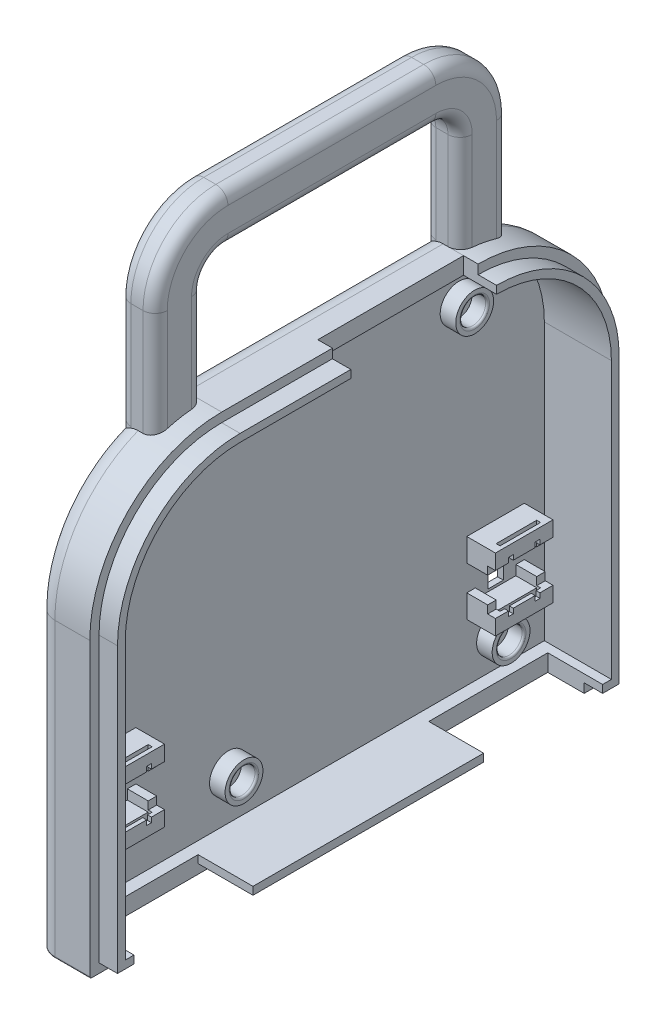
SolidWorks part; units mm, degrees
ref_plane "Front Plane" through (0, 0, 0) normal (0, 0, 1) x (1, 0, 0)
ref_plane "Top Plane" through (0, 0, 0) normal (0, 1, 0) x (1, 0, 0)
ref_plane "Right Plane" through (0, 0, 0) normal (1, 0, 0) x (0, 0, -1)
sketch "Sketch1" plane through (0, 0, 0) normal (1, 0, 0) x (0, 0, -1)
  line L0 (-52.8, 99.65) -> (52.8, 99.65)
  line L1 (-107.1, 45.35) -> (-107.1, -45.35)
  line L2 (-70, -75.35) -> (70, -75.35)
  line L3 (107.1, 45.35) -> (107.1, -45.35)
  line L4 (107.1, 0) -> (-107.1, 0) construction
  line L5 (0, 99.65) -> (0, -75.35) construction
  line L11 (107.1, -45.35) -> (107.1, -75.35)
  line L12 (107.1, -75.35) -> (70, -75.35)
  line L13 (-83.2, -21.7) -> (-76.8, -21.7)
  line L14 (-83.2, -21.7) -> (-83.2, -38.3)
  line L15 (-83.2, -38.3) -> (-76.8, -38.3)
  line L16 (-76.8, -21.7) -> (-76.8, -38.3)
  line L17 (-83.2, -21.7) -> (-76.8, -38.3) construction
  line L18 (-83.2, -38.3) -> (-76.8, -21.7) construction
  line L19 (76.8, -21.7) -> (83.2, -21.7)
  line L20 (76.8, -21.7) -> (76.8, -38.3)
  line L21 (76.8, -38.3) -> (83.2, -38.3)
  line L22 (83.2, -21.7) -> (83.2, -38.3)
  line L23 (76.8, -21.7) -> (83.2, -38.3) construction
  line L24 (76.8, -38.3) -> (83.2, -21.7) construction
  line L25 (80, -30) -> (-80, -30) construction
  line L27 (-107.1, -45.35) -> (-107.1, -75.35)
  line L28 (-107.1, -75.35) -> (-70, -75.35)
  arc A0 (52.8, 99.65) -> (107.1, 45.35) centre (52.8, 45.35) cw
  arc A1 (-52.8, 99.65) -> (-107.1, 45.35) centre (-52.8, 45.35) ccw
  point P16 (0, 0)
  point P17 (-80, -30)
  point P32 (80, -30)
  point P39 (-80, -30)
  point P40 (0, -30)
  dimension "D4" = 54.3
  dimension "D2" = 175
  dimension "D3" = 214.2
  dimension "D5" = 140
  dimension "D6" = 30
  dimension "D7" = 160
  dimension "D8" = 6.4
  dimension "D9" = 16.6
  dimension "D10" = 6.4
  dimension "D11" = 16.6
  dimension "D12" = 30
extrude "Boss-Extrude1" add sketch "Sketch1" along normal blind 2.4
sketch "Sketch9" plane through (2.4, 0, 0) normal (1, 0, 0) x (0, 0, -1)
  line L17 (52.8, 99.65) -> (-52.8, 99.65)
  line L31 (52.8, 99.65) -> (-52.8, 99.65)
  line L32 (-107.1, 45.35) -> (-107.1, -75.35)
  line L33 (-107.1, 45.35) -> (-107.1, -75.35)
  line L34 (-107.1, -75.35) -> (107.1, -75.35)
  line L39 (107.1, -75.35) -> (107.1, 45.35)
  line L43 (107.1, -75.35) -> (107.1, 45.35)
  line L45 (-107.1, -75.35) -> (107.1, -75.35)
  arc A15 (-52.8, 99.65) -> (-107.1, 45.35) centre (-52.8, 45.35) ccw
  arc A16 (-52.8, 99.65) -> (-107.1, 45.35) centre (-52.8, 45.35) ccw
  arc A17 (107.1, 45.35) -> (52.8, 99.65) centre (52.8, 45.35) ccw
  arc A18 (107.1, 45.35) -> (52.8, 99.65) centre (52.8, 45.35) ccw
  dimension "D1" = 0
sketch "Sketch10" plane through (2.4, 0, 0) normal (1, 0, 0) x (0, 0, -1)
  line L0 (65, -55.35) -> (0, -55.35) construction
  line L1 (-65, -55.35) -> (65, -55.35) construction
  line L2 (-65, -55.35) -> (-65, 54.65) construction
  line L3 (-65, 54.65) -> (65, 54.65) construction
  line L4 (65, -55.35) -> (65, 54.65) construction
  line L5 (-65, -55.35) -> (65, 54.65) construction
  line L6 (-65, 54.65) -> (65, -55.35) construction
  line L7 (0, -55.35) -> (-65, -55.35) construction
  line L8 (-107.1, -75.35) -> (107.1, -75.35) construction
  line L9 (0, -0.35) -> (0, 0) construction
  line L10 (0, -0.35) -> (0, -50.35) construction
  line L11 (-65, 54.65) -> (-65, 70.65) construction
  line L12 (-65, 70.65) -> (-70, 70.65) construction
  line L13 (0, -50.35) -> (-30, -50.35) construction
  circle A11 centre (-30, -50.35) radius 2.3
  circle A13 centre (65, 69.65) radius 2.3
  circle A14 centre (80, -55.35) radius 2.3
  circle A15 centre (-70, 70.65) radius 2.3
  point P0 (0, -0.35)
  point P11 (0, -55.35)
  point P12 (32.5, -55.35)
  point P14 (-32.5, -55.35)
  dimension "D3" = 15
  dimension "D4" = 20
  dimension "D8" = 4.6
  dimension "D1" = 130
  dimension "D2" = 110
  dimension "D5" = 50
  dimension "D6" = 15
  dimension "D7" = 16
  dimension "D9" = 5
  dimension "D10" = 30
extrude "Cut-Extrude1" cut sketch "Sketch10" against normal blind 100 and the other way blind 1000
sketch "Sketch12" plane through (2.4, 0, 0) normal (1, 0, 0) x (0, 0, -1)
  line L5 (-88.35, -38.3) -> (-88.35, -35.3)
  line L6 (-88.35, -38.3) -> (-88.35, -21.7) construction
  line L22 (71.65, -38.3) -> (71.65, -35.3)
  line L23 (71.65, -38.3) -> (71.65, -21.7) construction
  line L24 (71.65, -38.3) -> (88.35, -38.3) construction
  line L25 (88.35, -38.3) -> (88.35, -21.7) construction
  line L26 (71.65, -21.7) -> (88.35, -21.7) construction
  line L27 (71.65, -38.3) -> (88.35, -21.7) construction
  line L28 (88.35, -38.3) -> (71.65, -21.7) construction
  line L29 (71.65, -21.7) -> (71.65, -24.7)
  line L30 (88.35, -38.3) -> (88.35, -35.3)
  line L31 (88.35, -21.7) -> (88.35, -24.7)
  line L32 (71.65, -21.7) -> (88.35, -21.7) construction
  line L33 (88.35, -38.3) -> (71.65, -38.3) construction
  line L34 (88.35, -35.3) -> (91.85, -35.3)
  line L35 (71.65, -35.3) -> (68.15, -35.3)
  line L36 (68.15, -35.3) -> (68.15, -41.8)
  line L37 (68.15, -41.8) -> (91.85, -41.8)
  line L38 (91.85, -41.8) -> (91.85, -35.3)
  line L39 (71.65, -24.7) -> (68.15, -24.7)
  line L40 (68.15, -24.7) -> (68.15, -18.2)
  line L41 (68.15, -18.2) -> (91.85, -18.2)
  line L42 (91.85, -18.2) -> (91.85, -24.7)
  line L43 (91.85, -24.7) -> (88.35, -24.7)
  line L44 (83.2, -38.3) -> (76.8, -21.7) construction
  line L45 (83.2, -21.7) -> (76.8, -38.3) construction
  line L46 (-88.35, -38.3) -> (-71.65, -38.3) construction
  line L47 (-71.65, -38.3) -> (-71.65, -21.7) construction
  line L48 (-88.35, -21.7) -> (-71.65, -21.7) construction
  line L49 (-88.35, -38.3) -> (-71.65, -21.7) construction
  line L50 (-71.65, -38.3) -> (-88.35, -21.7) construction
  line L51 (-88.35, -21.7) -> (-88.35, -24.7)
  line L52 (-71.65, -38.3) -> (-71.65, -35.3)
  line L53 (-71.65, -21.7) -> (-71.65, -24.7)
  line L54 (-88.35, -21.7) -> (-71.65, -21.7) construction
  line L55 (-71.65, -38.3) -> (-88.35, -38.3) construction
  line L56 (-71.65, -35.3) -> (-68.15, -35.3)
  line L57 (-88.35, -35.3) -> (-91.85, -35.3)
  line L58 (-91.85, -35.3) -> (-91.85, -41.8)
  line L59 (-91.85, -41.8) -> (-68.15, -41.8)
  line L60 (-68.15, -41.8) -> (-68.15, -35.3)
  line L61 (-88.35, -24.7) -> (-91.85, -24.7)
  line L62 (-91.85, -24.7) -> (-91.85, -18.2)
  line L63 (-91.85, -18.2) -> (-68.15, -18.2)
  line L64 (-68.15, -18.2) -> (-68.15, -24.7)
  line L65 (-68.15, -24.7) -> (-71.65, -24.7)
  line L66 (-76.8, -38.3) -> (-83.2, -21.7) construction
  line L67 (-83.2, -38.3) -> (-76.8, -21.7) construction
  line L68 (-88.35, -21.7) -> (-88.35, -20.7047)
  line L69 (-88.35, -20.7047) -> (-71.65, -20.7047)
  line L70 (-71.65, -20.7047) -> (-71.65, -21.7)
  line L71 (-88.35, -38.3) -> (-88.35, -39.3)
  line L72 (-88.35, -39.3) -> (-71.65, -39.3)
  line L73 (-71.65, -39.3) -> (-71.65, -38.3)
  line L74 (88.35, -38.3) -> (88.35, -39.3)
  line L75 (88.35, -39.3) -> (71.65, -39.3)
  line L76 (71.65, -39.3) -> (71.65, -38.3)
  line L77 (88.35, -21.7) -> (88.35, -20.7047)
  line L78 (88.35, -20.7047) -> (71.65, -20.7047)
  line L79 (71.65, -20.7047) -> (71.65, -21.7)
  point P3 (-0.1438, 64.1533)
  point P4 (-80, -30)
  point P19 (80, -30)
  point P21 (-80, -30)
  point P30 (380.6447, 32.9453)
  point P31 (130.7088, -20.4974)
  point P32 (80, -30)
  point P49 (169.9078, -49.5925)
  dimension "D3" = 16.7
  dimension "D4" = 16.6
  dimension "D5" = 10.6
  dimension "D6" = 3.5
  dimension "D7" = 3.5
  dimension "D8" = 3.5
  dimension "D9" = 3.5
  dimension "D10" = 4.9497
  dimension "D11" = 16.7
  dimension "D12" = 16.6
  dimension "D13" = 10.6
  dimension "D14" = 3.5
  dimension "D15" = 3.5
  dimension "D16" = 3.5
  dimension "D17" = 3.5
  dimension "D18" = 4.9497
  dimension "D19" = 4.9497
  dimension "D20" = 7.3824
  dimension "D21" = 23.5468
  dimension "D22" = 24.088
  dimension "D23" = 4.9497
  dimension "D24" = 7.3824
  dimension "D25" = 23.5468
  dimension "D26" = 24.088
  dimension "D27" = 0.9953
  dimension "D28" = 1
  dimension "D29" = 1
  dimension "D30" = 0.9953
extrude "Boss-Extrude2" add sketch "Sketch12" along normal blind 8.6
sketch "Sketch14" plane through (11, 0, 0) normal (1, 0, 0) x (0, 0, -1)
  line L0 (-91.85, -18.2) -> (-91.85, -24.7) construction
  line L1 (-91.85, -18.2) -> (-68.15, -18.2)
  line L2 (-91.85, -18.2) -> (-91.85, -21.45)
  line L3 (-91.85, -21.45) -> (-68.15, -21.45)
  line L4 (-68.15, -18.2) -> (-68.15, -21.45)
  line L5 (-68.15, -18.2) -> (-91.85, -18.2) construction
  line L6 (-68.15, -24.7) -> (-68.15, -18.2) construction
  line L7 (-68.15, -41.8) -> (-68.15, -35.3) construction
  line L8 (-91.85, -41.8) -> (-68.15, -41.8)
  line L9 (-91.85, -41.8) -> (-91.85, -38.55)
  line L10 (-91.85, -38.55) -> (-68.15, -38.55)
  line L11 (-68.15, -41.8) -> (-68.15, -38.55)
  line L12 (91.85, -41.8) -> (91.85, -35.3) construction
  line L13 (68.15, -41.8) -> (91.85, -41.8)
  line L14 (68.15, -41.8) -> (68.15, -38.55)
  line L15 (68.15, -38.55) -> (91.85, -38.55)
  line L16 (91.85, -41.8) -> (91.85, -38.55)
  line L17 (91.85, -24.7) -> (91.85, -18.2) construction
  line L18 (68.15, -18.2) -> (91.85, -18.2)
  line L19 (68.15, -18.2) -> (68.15, -21.45)
  line L20 (68.15, -21.45) -> (91.85, -21.45)
  line L21 (91.85, -18.2) -> (91.85, -21.45)
extrude "Boss-Extrude3" add sketch "Sketch14" along normal blind 3.2
sketch "Sketch17" plane through (0, 0, 0) normal (1, 0, 0) x (0, 0, -1)
  line L0 (-103.9, 45.35) -> (-103.9, -72.15) construction
  line L1 (-103.9, -72.15) -> (103.9, -72.15) construction
  line L2 (103.9, -72.15) -> (103.9, 45.35) construction
  line L3 (52.8, 96.45) -> (-52.8, 96.45) construction
  line L4 (52.8, 99.65) -> (-52.8, 99.65)
  line L5 (-107.1, 45.35) -> (-107.1, -75.35)
  line L6 (-107.1, -75.35) -> (107.1, -75.35)
  line L7 (107.1, -75.35) -> (107.1, 45.35)
  line L8 (52.8, 99.65) -> (-52.8, 99.65) construction
  line L9 (-107.1, 45.35) -> (-107.1, -75.35) construction
  line L11 (107.1, -75.35) -> (107.1, 45.35) construction
  line L16 (100.1, -68.35) -> (100.1, 45.35)
  line L17 (52.8, 92.65) -> (-52.8, 92.65)
  line L18 (-100.1, 45.35) -> (-100.1, -68.35)
  line L19 (-100.1, -68.35) -> (100.1, -68.35)
  line L24 (52.8, 95.85) -> (-52.8, 95.85)
  line L25 (-103.3, 45.35) -> (-103.3, -71.55)
  line L27 (103.3, -71.55) -> (103.3, 45.35)
  line L28 (-107.1, -75.35) -> (107.1, -75.35) construction
  line L29 (-103.3, -71.55) -> (103.3, -71.55) construction
  line L31 (-103.3, -71.55) -> (103.3, -71.55)
  arc A0 (103.9, 45.35) -> (52.8, 96.45) centre (52.8, 45.35) ccw construction
  arc A1 (-52.8, 96.45) -> (-103.9, 45.35) centre (-52.8, 45.35) ccw construction
  arc A2 (-52.8, 99.65) -> (-107.1, 45.35) centre (-52.8, 45.35) ccw
  arc A3 (107.1, 45.35) -> (52.8, 99.65) centre (52.8, 45.35) ccw
  arc A4 (-52.8, 99.65) -> (-107.1, 45.35) centre (-52.8, 45.35) ccw construction
  arc A5 (107.1, 45.35) -> (52.8, 99.65) centre (52.8, 45.35) ccw construction
  arc A8 (100.1, 45.35) -> (52.8, 92.65) centre (52.8, 45.35) ccw
  arc A9 (-52.8, 92.65) -> (-100.1, 45.35) centre (-52.8, 45.35) ccw
  arc A12 (-52.8, 95.85) -> (-103.3, 45.35) centre (-52.8, 45.35) ccw
  arc A13 (103.3, 45.35) -> (52.8, 95.85) centre (52.8, 45.35) ccw
  dimension "D4" = 167.4
  dimension "D5" = 206.6
  dimension "D7" = 207.8
  dimension "D8" = 214.2
  dimension "D9" = 3.2
  dimension "D2" = 3.2
  dimension "D10" = 3.2
  dimension "D11" = 3.2
  dimension "D1" = 0
  dimension "D3" = 3.2
  dimension "D6" = 0.6
extrude "Boss-Extrude4" add sketch "Sketch17" along normal blind 30
sketch "Sketch21" plane through (2.4, 0, 0) normal (1, 0, 0) x (0, 0, -1)
  line L4 (-107.1, -75.35) -> (107.1, -75.35)
  line L6 (-107.1, -75.35) -> (107.1, -75.35)
  line L8 (52.8, 99.65) -> (-52.8, 99.65)
  line L9 (-107.1, 45.35) -> (-107.1, -75.35)
  line L11 (107.1, -75.35) -> (107.1, 45.35)
  line L12 (52.8, 99.65) -> (-52.8, 99.65)
  line L13 (-107.1, 45.35) -> (-107.1, -75.35)
  line L15 (107.1, -75.35) -> (107.1, 45.35)
  arc A4 (-52.8, 99.65) -> (-107.1, 45.35) centre (-52.8, 45.35) ccw
  arc A5 (107.1, 45.35) -> (52.8, 99.65) centre (52.8, 45.35) ccw
  arc A6 (-52.8, 99.65) -> (-107.1, 45.35) centre (-52.8, 45.35) ccw
  arc A7 (107.1, 45.35) -> (52.8, 99.65) centre (52.8, 45.35) ccw
  dimension "D1" = 0
sketch "Sketch22" plane through (2.4, 0, 0) normal (1, 0, 0) x (0, 0, -1)
  line L0 (-107.1, -75.35) -> (107.1, -75.35) construction
  line L1 (-107.1, -75.35) -> (107.1, -75.35)
  line L21 (52.8, 99.65) -> (-52.8, 99.65)
  line L22 (107.1, -75.35) -> (107.1, 45.35)
  line L24 (-107.1, 45.35) -> (-107.1, -75.35)
  line L25 (52.8, 99.65) -> (-52.8, 99.65)
  line L26 (107.1, -75.35) -> (107.1, 45.35)
  line L28 (-107.1, 45.35) -> (-107.1, -75.35)
  line L44 (-103.3, -71.55) -> (103.3, -71.55)
  line L45 (103.3, -71.55) -> (103.3, 45.35)
  line L46 (52.8, 95.85) -> (-52.8, 95.85)
  line L47 (-103.3, 45.35) -> (-103.3, -71.55)
  line L48 (-103.3, -71.55) -> (103.3, -71.55)
  line L49 (103.3, -71.55) -> (103.3, 45.35)
  line L50 (52.8, 95.85) -> (-52.8, 95.85)
  line L51 (-103.3, 45.35) -> (-103.3, -71.55)
  arc A6 (-52.8, 99.65) -> (-107.1, 45.35) centre (-52.8, 45.35) ccw
  arc A7 (107.1, 45.35) -> (52.8, 99.65) centre (52.8, 45.35) ccw
  arc A8 (-52.8, 99.65) -> (-107.1, 45.35) centre (-52.8, 45.35) ccw
  arc A9 (107.1, 45.35) -> (52.8, 99.65) centre (52.8, 45.35) ccw
  arc A20 (103.3, 45.35) -> (52.8, 95.85) centre (52.8, 45.35) ccw
  arc A21 (-52.8, 95.85) -> (-103.3, 45.35) centre (-52.8, 45.35) ccw
  arc A22 (103.3, 45.35) -> (52.8, 95.85) centre (52.8, 45.35) ccw
  arc A23 (-52.8, 95.85) -> (-103.3, 45.35) centre (-52.8, 45.35) ccw
  dimension "D1" = 0
  dimension "D2" = 0
extrude "Boss-Extrude7" add sketch "Sketch22" along normal blind 20
sketch "Sketch23" plane through (0, -75.35, 0) normal (0, -1, 0) x (1, 0, 0)
  line L0 (0, 99.1) -> (0, 107.1)
  line L1 (0, 107.1) -> (8, 107.1)
  line L2 (8, -107.1) -> (0, -107.1)
  line L3 (0, -107.1) -> (0, -99.1)
  line L8 (0, 107.1) -> (0, -107.1)
  line L9 (0, -107.1) -> (22.4, -107.1)
  line L10 (22.4, -107.1) -> (22.4, 107.1)
  line L11 (22.4, 107.1) -> (0, 107.1)
  line L12 (0, 99.1) -> (0, -99.1) construction
  line L13 (8, -107.1) -> (22.4, -107.1) construction
  line L15 (22.4, 107.1) -> (8, 107.1) construction
  arc A0 (0, 99.1) -> (8, 107.1) centre (8, 99.1) cw
  arc A1 (0, -99.1) -> (8, -107.1) centre (8, -99.1) ccw
  dimension "D2" = 8
  dimension "D1" = 0
extrude "Cut-Extrude4" cut sketch "Sketch23" against normal through all
fillet "Fillet4" radius 8 3 edges at (0, 92.7258, 79.3335) (0, 99.65, 0) (0, 92.7258, -79.3335)
sketch "Sketch26" plane through (22.4, 0, 0) normal (1, 0, 0) x (0, 0, -1)
  line L1 (-47.5, -68.3365) -> (47.5, -68.3365)
  line L2 (47.5, -68.3365) -> (47.5, -71.55)
  line L6 (47.5, -71.55) -> (-47.5, -71.55)
  line L7 (-47.5, -71.55) -> (-47.5, -68.3365)
  line L8 (-103.3, -71.55) -> (103.3, -71.55) construction
  line L9 (-96.5, -79.5369) -> (96.5, -79.5369)
  line L10 (-96.5, -79.5369) -> (-96.5, -63.5631)
  line L11 (-96.5, -63.5631) -> (96.5, -63.5631)
  line L12 (96.5, -79.5369) -> (96.5, -63.5631)
  line L13 (-96.5, -79.5369) -> (96.5, -63.5631) construction
  line L14 (-96.5, -63.5631) -> (96.5, -79.5369) construction
  line L15 (107.1, -75.35) -> (107.1, 45.35) construction
  point P0 (0, -71.55)
  point P9 (0, -68.3365)
  point P13 (0, -68.3365)
  point P16 (0, -68.3365)
  dimension "D1" = 10.6
  dimension "D2" = 15.9739
  dimension "D3" = 95
  dimension "D4" = 3.2135
extrude "Cut-Extrude7" cut sketch "Sketch26" against normal blind 15 and the other way blind 20
sketch "Sketch28" plane through (0, 99.65, 0) normal (0, 1, 0) x (1, 0, 0)
  line L0 (22.4, 52.8) -> (16.4, 52.8)
  line L1 (22.4, 52.8) -> (8, 52.8) construction
  line L2 (16.4, 52.8) -> (16.4, -7.2)
  line L3 (16.4, -7.2) -> (51.1003, -7.2)
  line L4 (51.1003, -7.2) -> (51.1003, 52.8)
  line L5 (51.1003, 52.8) -> (22.4, 52.8)
  dimension "D1" = 6
  dimension "D2" = 60
extrude "Cut-Extrude8" cut sketch "Sketch28" against normal blind 10
sketch "Sketch29" plane through (0, -21.45, 0) normal (0, -1, 0) x (1, 0, 0)
  line L12 (11, -88.35) -> (11, -91.85) construction
  line L13 (11, -82.1) -> (11, -98.1)
  line L14 (11, -98.1) -> (12.5, -98.1)
  line L15 (12.5, -98.1) -> (12.5, -82.1)
  line L16 (12.5, -82.1) -> (11, -82.1)
  line L23 (2.4, 68.15) -> (14.2, 68.15)
  line L24 (2.4, 91.85) -> (2.4, 68.15)
  line L25 (14.2, 91.85) -> (2.4, 91.85)
  line L26 (14.2, 68.15) -> (14.2, 91.85)
  line L31 (2.4, 68.15) -> (14.2, 68.15) construction
  line L32 (2.4, 91.85) -> (2.4, 68.15) construction
  line L33 (14.2, 91.85) -> (2.4, 91.85) construction
  line L34 (14.2, 68.15) -> (14.2, 91.85) construction
  point P1 (11, -90.1)
  point P9 (11, -90.1)
  point P14 (11, -90.1)
  dimension "D1" = 0
  dimension "D3" = 16
  dimension "D4" = 1.5
sketch "Sketch30" plane through (2.4, 0, 0) normal (1, 0, 0) x (0, 0, -1)
  circle A0 centre (-70, 70.65) radius 5.3
  circle A1 centre (65, 69.65) radius 5.3
  circle A2 centre (-30, -50.35) radius 5.3
  circle A3 centre (80, -55.35) radius 5.3
  circle A5 centre (65, 69.65) radius 7.8
  circle A6 centre (80, -55.35) radius 7.8
  circle A7 centre (-30, -50.35) radius 7.8
  circle A8 centre (-70, 70.65) radius 7.8
  dimension "D1" = 10.6
  dimension "D2" = 15.6
extrude "Boss-Extrude8" add sketch "Sketch30" along normal blind 6.4
fillet "Fillet7" radius 0.8 4 edges at (8.8, -55.35, -85.3) (8.8, -50.35, 24.7) (8.8, 69.65, -70.3) (8.8, 70.65, 64.7)
fillet "Fillet8" radius 0.8 5 edges at (15.2, -75.35, 107.1) (2.3431, -75.35, 104.7569) (15.2, -75.35, -107.1) (2.3431, -75.35, -104.7569) (0, -75.35, 0)
sketch "Sketch31" plane through (0, 0, 0) normal (1, 0, 0) x (0, 0, -1)
  line L0 (-52.8, 99.65) -> (-52.8, 139.65)
  line L1 (-42.8, 149.65) -> (42.8, 149.65)
  line L2 (52.8, 139.65) -> (52.8, 99.65)
  line L3 (52.8, 99.65) -> (-52.8, 99.65) construction
  line L4 (-72.8, 95.8326) -> (-72.8, 139.65)
  line L5 (-42.8, 169.65) -> (42.8, 169.65)
  line L6 (72.8, 139.65) -> (72.8, 95.8326)
  arc A2 (-52.8, 99.65) -> (-107.1, 45.35) centre (-52.8, 45.35) ccw construction
  arc A3 (107.1, 45.35) -> (52.8, 99.65) centre (52.8, 45.35) ccw construction
  arc A4 (-52.8, 99.65) -> (-72.8, 95.8326) centre (-52.8, 45.35) ccw
  arc A5 (72.8, 95.8326) -> (52.8, 99.65) centre (52.8, 45.35) ccw
  arc A9 (-52.8, 139.65) -> (-42.8, 149.65) centre (-42.8, 139.65) cw
  arc A10 (42.8, 149.65) -> (52.8, 139.65) centre (42.8, 139.65) cw
  arc A11 (72.8, 139.65) -> (42.8, 169.65) centre (42.8, 139.65) ccw
  arc A12 (-42.8, 169.65) -> (-72.8, 139.65) centre (-42.8, 139.65) ccw
  point P13 (52.8, 149.65)
  dimension "D2" = 10
  dimension "D1" = 50
  dimension "D3" = 20
  dimension "D4" = 20
extrude "Boss-Extrude9" add sketch "Sketch31" along normal blind 15
fillet "Fillet9" radius 5 20 edges at (0, 117.7413, -72.8) (0, 160.8632, -64.0132) (0, 117.7413, 72.8) (0, 160.8632, 64.0132) (0, 119.65, 52.8) (0, 146.7211, 49.8711) (0, 149.65, 0) (0, 146.7211, -49.8711) (15, 119.65, 52.8) (15, 119.65, -52.8) (15, 146.7211, -49.8711) (15, 149.65, 0) (15, 117.7413, -72.8) (15, 160.8632, -64.0132) (15, 169.65, 0) (15, 117.7413, 72.8) (0, 169.65, 0) (0, 119.65, -52.8) (15, 146.7211, 49.8711) (15, 160.8632, 64.0132)
sketch "Sketch32" plane through (0, 0, 0) normal (-1, 0, 0) x (0, 0, 1)
  line L0 (52.8, 99.65) -> (52.8, 91.65)
  line L1 (72.8, 95.8326) -> (72.8, 87.1075)
  line L2 (-72.8, 95.8326) -> (-72.8, 87.1075)
  line L3 (-52.8, 99.65) -> (-52.8, 91.65)
  arc A0 (67.8, 97.5371) -> (57.8, 99.4193) centre (52.8, 45.35) ccw construction
  arc A1 (-52.8, 91.65) -> (-99.1, 45.35) centre (-52.8, 45.35) ccw construction
  arc A2 (-52.8, 99.65) -> (-57.8, 99.4193) centre (-52.8, 45.35) ccw construction
  arc A3 (-57.8, 99.4193) -> (-67.8, 97.5371) centre (-52.8, 45.35) ccw construction
  arc A4 (-67.8, 97.5371) -> (-72.8, 95.8326) centre (-52.8, 45.35) ccw construction
  arc A5 (72.8, 95.8326) -> (67.8, 97.5371) centre (52.8, 45.35) ccw construction
  arc A6 (57.8, 99.4193) -> (52.8, 99.65) centre (52.8, 45.35) ccw construction
  arc A7 (99.1, 45.35) -> (52.8, 91.65) centre (52.8, 45.35) ccw construction
  arc A8 (67.8, 97.5371) -> (57.8, 99.4193) centre (52.8, 45.35) ccw
  arc A9 (-52.8, 91.65) -> (-72.8, 87.1075) centre (-52.8, 45.35) ccw
  arc A10 (-52.8, 99.65) -> (-57.8, 99.4193) centre (-52.8, 45.35) ccw
  arc A11 (-57.8, 99.4193) -> (-67.8, 97.5371) centre (-52.8, 45.35) ccw
  arc A12 (-67.8, 97.5371) -> (-72.8, 95.8326) centre (-52.8, 45.35) ccw
  arc A13 (72.8, 95.8326) -> (67.8, 97.5371) centre (52.8, 45.35) ccw
  arc A14 (57.8, 99.4193) -> (52.8, 99.65) centre (52.8, 45.35) ccw
  arc A15 (72.8, 87.1075) -> (52.8, 91.65) centre (52.8, 45.35) ccw
extrude "Boss-Extrude10" add sketch "Sketch32" against normal up to body separate body
fillet "Fillet10" radius 5 4 edges at (0, 91.47, 72.8) (0, 95.65, 52.8) (0, 95.65, -52.8) (0, 91.47, -72.8)
sketch "Sketch33" plane through (0, -38.55, 0) normal (0, 1, 0) x (1, 0, 0)
  line L0 (11, 91.85) -> (11, 88.35) construction
  line L1 (11, 88.35) -> (11, 71.65) construction
  line L2 (11, 71.65) -> (11, 68.15) construction
  line L3 (11, 68.15) -> (14.2, 68.15) construction
  line L4 (14.2, 68.15) -> (14.2, 91.85) construction
  line L5 (14.2, 91.85) -> (11, 91.85) construction
  line L6 (11, -68.15) -> (11, -71.65) construction
  line L7 (11, -71.65) -> (11, -88.35) construction
  line L8 (11, -88.35) -> (11, -91.85) construction
  line L9 (11, -91.85) -> (14.2, -91.85) construction
  line L10 (14.2, -91.85) -> (14.2, -68.15) construction
  line L11 (14.2, -68.15) -> (11, -68.15) construction
  line L12 (11, 91.85) -> (11, 88.35) construction
  line L13 (11, 88.35) -> (11, 71.65)
  line L14 (11, 71.65) -> (11, 68.15) construction
  line L15 (11, 68.15) -> (14.2, 68.15) construction
  line L16 (14.2, 68.15) -> (14.2, 91.85) construction
  line L17 (14.2, 91.85) -> (11, 91.85) construction
  line L18 (11, -68.15) -> (11, -71.65) construction
  line L19 (11, -71.65) -> (11, -88.35)
  line L20 (11, -88.35) -> (11, -91.85) construction
  line L21 (11, -91.85) -> (14.2, -91.85) construction
  line L22 (14.2, -91.85) -> (14.2, -68.15) construction
  line L23 (14.2, -68.15) -> (11, -68.15) construction
  line L24 (11, -88.35) -> (12.6001, -88.35)
  line L25 (12.6001, -88.35) -> (12.6001, -71.65)
  line L26 (12.6001, -71.65) -> (11, -71.65)
  line L27 (11, 71.65) -> (12.6001, 71.65)
  line L28 (12.6001, 71.65) -> (12.6001, 88.35)
  line L29 (12.6001, 88.35) -> (11, 88.35)
  dimension "D1" = 1.6001
  dimension "D2" = 1.6001
extrude "Cut-Extrude9" cut sketch "Sketch33" against normal up to surface and the other way up to surface up to face at (8.3, -41.8, -80) other way up to face at (8.3, -18.2, -80)
sketch "Sketch34" plane through (14.2, 0, 0) normal (1, 0, 0) x (0, 0, -1)
  line L0 (68.15, -21.45) -> (91.85, -21.45) construction
  line L2 (91.85, -38.55) -> (68.15, -38.55) construction
  line L3 (-68.15, -38.55) -> (-91.85, -38.55) construction
  line L4 (-91.85, -21.45) -> (-68.15, -21.45) construction
  line L12 (68.15, -21.45) -> (91.85, -21.45) construction
  line L19 (91.85, -38.55) -> (68.15, -38.55) construction
  line L25 (-68.15, -38.55) -> (-91.85, -38.55) construction
  line L31 (-91.85, -21.45) -> (-68.15, -21.45) construction
  line L48 (-74.5, -38.55) -> (-85.5, -38.55) construction
  line L61 (-74.5, -21.45) -> (-85.5, -21.45) construction
  line L62 (85.5, -21.45) -> (74.5, -21.45) construction
  line L64 (85.5, -38.55) -> (74.5, -38.55) construction
  line L77 (-75.5, -38.55) -> (-73.5, -38.55)
  line L82 (-75.5, -38.55) -> (-75.5, -40.55)
  line L83 (-75.5, -40.55) -> (-73.5, -40.55)
  line L88 (-73.5, -38.55) -> (-73.5, -40.55)
  line L89 (-84.5, -38.55) -> (-86.5, -38.55)
  line L94 (-84.5, -38.55) -> (-84.5, -40.55)
  line L95 (-84.5, -40.55) -> (-86.5, -40.55)
  line L100 (-86.5, -38.55) -> (-86.5, -40.55)
  line L101 (-84.5, -21.45) -> (-86.5, -21.45)
  line L106 (-84.5, -21.45) -> (-84.5, -19.45)
  line L107 (-84.5, -19.45) -> (-86.5, -19.45)
  line L112 (-86.5, -21.45) -> (-86.5, -19.45)
  line L113 (-75.5, -21.45) -> (-73.5, -21.45)
  line L114 (-75.5, -21.45) -> (-75.5, -19.45)
  line L115 (-75.5, -19.45) -> (-73.5, -19.45)
  line L116 (-73.5, -21.45) -> (-73.5, -19.45)
  line L117 (75.5, -21.45) -> (73.5, -21.45)
  line L118 (75.5, -21.45) -> (75.5, -19.45)
  line L119 (75.5, -19.45) -> (73.5, -19.45)
  line L120 (73.5, -21.45) -> (73.5, -19.45)
  line L121 (75.5, -38.55) -> (73.5, -38.55)
  line L122 (75.5, -38.55) -> (75.5, -40.55)
  line L123 (75.5, -40.55) -> (73.5, -40.55)
  line L124 (73.5, -38.55) -> (73.5, -40.55)
  line L125 (84.5, -38.55) -> (86.5, -38.55)
  line L126 (84.5, -38.55) -> (84.5, -40.55)
  line L127 (84.5, -40.55) -> (86.5, -40.55)
  line L128 (86.5, -38.55) -> (86.5, -40.55)
  line L129 (84.5, -21.45) -> (86.5, -21.45)
  line L130 (84.5, -21.45) -> (84.5, -19.45)
  line L131 (84.5, -19.45) -> (86.5, -19.45)
  line L132 (86.5, -21.45) -> (86.5, -19.45)
  point P0 (80, -38.55)
  point P9 (80, -21.45)
  point P10 (-80, -21.45)
  point P11 (-80, -38.55)
  point P15 (-80, -38.55)
  point P18 (-80, -21.45)
  point P21 (80, -21.45)
  point P24 (80, -38.55)
  point P56 (-85.5, -38.55)
  point P57 (-74.5, -21.45)
  point P58 (-74.5, -38.55)
  point P59 (-85.5, -21.45)
  point P60 (74.5, -21.45)
  point P61 (85.5, -21.45)
  point P62 (85.5, -38.55)
  point P64 (85.5, -21.45)
  point P65 (74.5, -21.45)
  point P66 (74.5, -38.55)
  point P67 (-74.5, -21.45)
  point P68 (-85.5, -21.45)
  point P69 (-74.5, -38.55)
  dimension "D2" = 2
  dimension "D1" = 11
extrude "Cut-Extrude11" cut sketch "Sketch34" against normal blind 3
sketch "Sketch36" plane through (0, -18.2, 0) normal (0, 1, 0) x (1, 0, 0)
  line L0 (2.4, 91.85) -> (2.4, 68.15) construction
  line L1 (2.4, 68.15) -> (14.2, 68.15) construction
  line L2 (14.2, 68.15) -> (14.2, 91.85) construction
  line L3 (14.2, 91.85) -> (2.4, 91.85) construction
  line L4 (2.4, -68.15) -> (2.4, -91.85) construction
  line L5 (2.4, -91.85) -> (14.2, -91.85) construction
  line L6 (14.2, -91.85) -> (14.2, -68.15) construction
  line L7 (14.2, -68.15) -> (2.4, -68.15) construction
  line L8 (2.4, 91.85) -> (2.4, 68.15)
  line L9 (2.4, 68.15) -> (14.2, 68.15)
  line L10 (14.2, 68.15) -> (14.2, 91.85)
  line L11 (14.2, 91.85) -> (2.4, 91.85)
  line L12 (2.4, -68.15) -> (2.4, -91.85)
  line L13 (2.4, -91.85) -> (14.2, -91.85)
  line L14 (14.2, -91.85) -> (14.2, -68.15)
  line L15 (14.2, -68.15) -> (2.4, -68.15)
  line L16 (12.6001, 71.65) -> (11, 71.65) construction
  line L17 (12.6001, 88.35) -> (12.6001, 71.65) construction
  line L18 (11, 71.65) -> (11, 88.35) construction
  line L19 (11, 88.35) -> (12.6001, 88.35) construction
  line L20 (11, -71.65) -> (12.6001, -71.65) construction
  line L21 (12.6001, -88.35) -> (11, -88.35) construction
  line L22 (12.6001, -71.65) -> (12.6001, -88.35) construction
  line L23 (11, -88.35) -> (11, -71.65) construction
  line L24 (12.6001, 71.65) -> (11, 71.65)
  line L25 (12.6001, 88.35) -> (12.6001, 71.65)
  line L26 (11, 71.65) -> (11, 88.35)
  line L27 (11, 88.35) -> (12.6001, 88.35)
  line L28 (11, -71.65) -> (12.6001, -71.65)
  line L29 (12.6001, -88.35) -> (11, -88.35)
  line L30 (12.6001, -71.65) -> (12.6001, -88.35)
  line L31 (11, -88.35) -> (11, -71.65)
extrude "Boss-Extrude11" add sketch "Sketch36" along normal blind 3
sketch "Sketch37" plane through (0, -41.8, 0) normal (0, -1, 0) x (1, 0, 0)
  line L0 (2.4, -68.15) -> (2.4, -91.85) construction
  line L1 (2.4, -91.85) -> (14.2, -91.85) construction
  line L2 (14.2, -91.85) -> (14.2, -68.15) construction
  line L3 (14.2, -68.15) -> (2.4, -68.15) construction
  line L4 (2.4, 91.85) -> (2.4, 68.15) construction
  line L5 (2.4, 68.15) -> (14.2, 68.15) construction
  line L6 (14.2, 68.15) -> (14.2, 91.85) construction
  line L7 (14.2, 91.85) -> (2.4, 91.85) construction
  line L8 (11, 71.65) -> (12.6001, 71.65) construction
  line L9 (12.6001, 71.65) -> (12.6001, 88.35) construction
  line L10 (11, 88.35) -> (11, 71.65) construction
  line L11 (12.6001, 88.35) -> (11, 88.35) construction
  line L12 (12.6001, -71.65) -> (11, -71.65) construction
  line L13 (12.6001, -88.35) -> (12.6001, -71.65) construction
  line L14 (11, -88.35) -> (12.6001, -88.35) construction
  line L15 (2.4, -68.15) -> (2.4, -91.85)
  line L16 (2.4, -91.85) -> (14.2, -91.85)
  line L17 (14.2, -91.85) -> (14.2, -68.15)
  line L18 (14.2, -68.15) -> (2.4, -68.15)
  line L19 (2.4, 91.85) -> (2.4, 68.15)
  line L20 (2.4, 68.15) -> (14.2, 68.15)
  line L21 (14.2, 68.15) -> (14.2, 91.85)
  line L22 (14.2, 91.85) -> (2.4, 91.85)
  line L23 (11, 71.65) -> (12.6001, 71.65)
  line L24 (12.6001, 71.65) -> (12.6001, 88.35)
  line L25 (11, 88.35) -> (11, 71.65)
  line L26 (12.6001, 88.35) -> (11, 88.35)
  line L27 (12.6001, -71.65) -> (11, -71.65)
  line L28 (12.6001, -88.35) -> (12.6001, -71.65)
  line L29 (11, -88.35) -> (12.6001, -88.35)
  line L30 (11, -71.65) -> (11, -88.35) construction
  line L31 (11, -71.65) -> (11, -88.35)
extrude "Boss-Extrude12" add sketch "Sketch37" along normal blind 3
